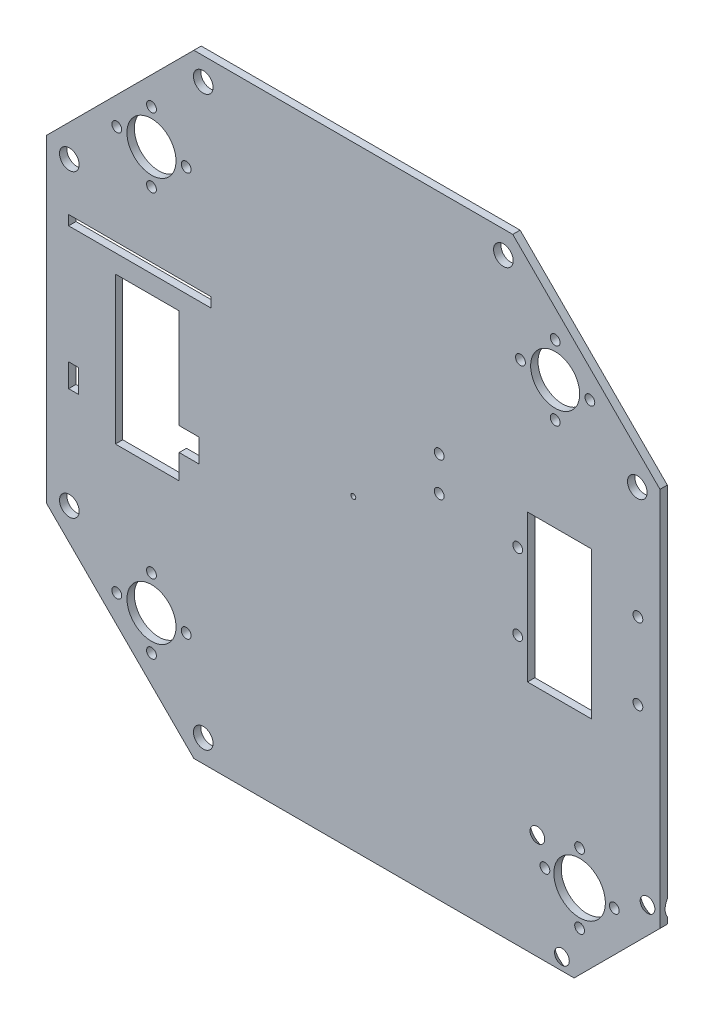
SolidWorks part; units mm, degrees
ref_plane "Plan de face" through (0, 0, 0) normal (0, 0, 1) x (1, 0, 0)
ref_plane "Plan de dessus" through (0, 0, 0) normal (0, 1, 0) x (1, 0, 0)
ref_plane "Plan de droite" through (0, 0, 0) normal (1, 0, 0) x (0, 0, -1)
sketch "Esquisse1" plane through (0, 0, 0) normal (0, 0, 1) x (1, 0, 0)
  line L0 (-246.0478, 39) -> (-186.0478, -21)
  line L1 (-31.0478, -21) -> (-186.0478, -21)
  line L2 (3.9522, 14) -> (3.9522, 169)
  line L3 (-56.0478, 229) -> (-186.0478, 229)
  line L4 (-246.0478, 39) -> (-246.0478, 169)
  line L5 (-246.0478, 169) -> (-186.0478, 229)
  line L6 (-56.0478, 229) -> (3.9522, 169)
  line L7 (-28.8088, 11.8727) -> (-35.8798, 4.8016) construction
  line L8 (-121.0478, 229) -> (-121.0478, -21) construction
  line L9 (-192.0478, 74) -> (-192.0478, 84)
  line L10 (-213.3199, 11.7279) -> (-186.0478, 39) construction
  line L11 (-192.0478, 93.5) -> (-192.0478, 134)
  line L12 (-218.0478, 104) -> (-218.0478, 134)
  line L13 (-218.0478, 134) -> (-192.0478, 134)
  line L14 (-218.0478, 104) -> (-218.0478, 74)
  line L15 (-218.0478, 79) -> (-187.0957, 79) construction
  line L16 (-35.8798, 4.8016) -> (-42.9508, 11.8726) construction
  line L17 (-218.0478, 74) -> (-192.0478, 74)
  line L18 (-186.0478, 229) -> (-182.221, 219.7612) construction
  line L19 (-24.0478, 74) -> (-24.0478, 134)
  line L20 (-193.3199, 11.7279) -> (-229.7432, 11.7279) construction
  line L21 (-210.391, 14.6569) -> (-225.6191, 29.8849) construction
  line L22 (-237.0957, 145.5) -> (-179.0957, 145.5)
  line L23 (-237.0957, 84) -> (-237.0957, 93.5)
  line L24 (-237.0957, 84) -> (-233.0957, 84)
  line L25 (-179.0957, 145.5) -> (-179.0957, 141.5)
  line L26 (-184.0478, 84) -> (-192.0478, 84)
  line L27 (-237.0957, 141.5) -> (-179.0957, 141.5)
  line L28 (-237.0957, 93.5) -> (-233.0957, 93.5)
  line L29 (-233.0957, 84) -> (-233.0957, 93.5)
  line L30 (-246.0478, 64.4558) -> (-160.592, -21) construction
  line L31 (-192.0478, 93.5) -> (-184.0478, 93.5)
  line L32 (-237.0957, 141.5) -> (-237.0957, 145.5)
  line L33 (-184.0478, 93.5) -> (-184.0478, 84)
  line L34 (-210.391, 28.799) -> (-219.2314, 19.9586) construction
  line L35 (-24.0478, 134) -> (-50.0478, 134)
  line L36 (-50.0478, 134) -> (-50.0478, 74)
  line L37 (-50.0478, 74) -> (-24.0478, 74)
  line L38 (-24.0478, 104) -> (-5.0478, 104) construction
  line L39 (-5.0478, 104) -> (-5.0478, 119.5) construction
  line L40 (-42.9508, 11.8726) -> (-28.8087, 26.0148) construction
  line L41 (-28.8087, 26.0148) -> (-14.6666, 11.8726) construction
  line L42 (-14.6666, 11.8726) -> (-28.8087, -2.2695) construction
  line L43 (3.9522, -21) -> (-51.476, 34.4281) construction
  line L44 (-28.8088, 11.8727) -> (-14.4935, -2.0941) construction
  line L45 (3.9522, 14) -> (-31.0478, -21)
  circle A0 centre (-42.9508, 11.8726) radius 2
  circle A1 centre (-1.1223, 19.7714) radius 3
  circle A2 centre (-36.0228, -16) radius 3
  circle A3 centre (-28.8087, 26.0148) radius 2
  circle A4 centre (-203.3199, 21.7279) radius 10
  circle A5 centre (-203.3199, 7.5858) radius 2
  circle A6 centre (-189.1778, 21.7279) radius 2
  circle A7 centre (-203.3199, 35.8701) radius 2
  circle A8 centre (-28.8088, 11.8727) radius 10.5
  circle A9 centre (-217.4621, 21.7279) radius 2
  circle A10 centre (-38.7758, 172.1299) radius 2
  circle A11 centre (-52.9179, 186.2721) radius 2
  circle A12 centre (-38.7758, 200.4142) radius 2
  circle A13 centre (-24.6336, 186.2721) radius 2
  circle A14 centre (-38.7758, 186.2721) radius 10
  circle A15 centre (-203.3199, 186.2721) radius 10
  circle A16 centre (-217.4621, 186.2721) radius 2
  circle A17 centre (-203.3199, 200.4142) radius 2
  circle A18 centre (-189.1778, 186.2721) radius 2
  circle A19 centre (-203.3199, 172.1299) radius 2
  circle A20 centre (-182.221, -11.7612) radius 4
  circle A21 centre (-182.221, 219.7612) radius 4
  circle A22 centre (-236.809, 42.8268) radius 4
  circle A23 centre (-5.0478, 119.5) radius 2
  circle A24 centre (-236.809, 165.1732) radius 4
  circle A25 centre (-28.8087, -2.2695) radius 2
  circle A26 centre (-14.6666, 11.8726) radius 2
  circle A27 centre (-5.2866, 165.1732) radius 4
  circle A28 centre (-59.8747, 219.7612) radius 4
  circle A29 centre (-5.0478, 88.5) radius 2
  circle A30 centre (-86.0478, 136.5) radius 2
  circle A31 centre (-86.0478, 122.5) radius 2
  circle A32 centre (-54.0478, 119.5) radius 2
  circle A33 centre (-54.0478, 88.5) radius 2
  circle A34 centre (-46.0228, 22) radius 3
  circle A35 centre (-36.0228, 22) radius 3 [skipped]
  circle A36 centre (-46.0228, -16) radius 3 [skipped]
  circle A38 centre (-121.0478, 104) radius 1
  dimension "D3" = 9
  dimension "D2" = 15.5
  dimension "D1" = 19
  dimension "D5" = 14
  dimension "D6" = 21
  dimension "D7" = 43
  dimension "D4" = 26
  dimension "D8" = 90
  dimension "D9" = 32.8727
  dimension "D10" = 46.5
extrude "Extrusion1" add sketch "Esquisse1" along normal blind 3
chamfer "Chanfrein2" distance 3 angle 45 3 edges at (-4.1223, 19.7714, 0) (-33.0228, -16, 0) (-43.0228, 22, 0)
